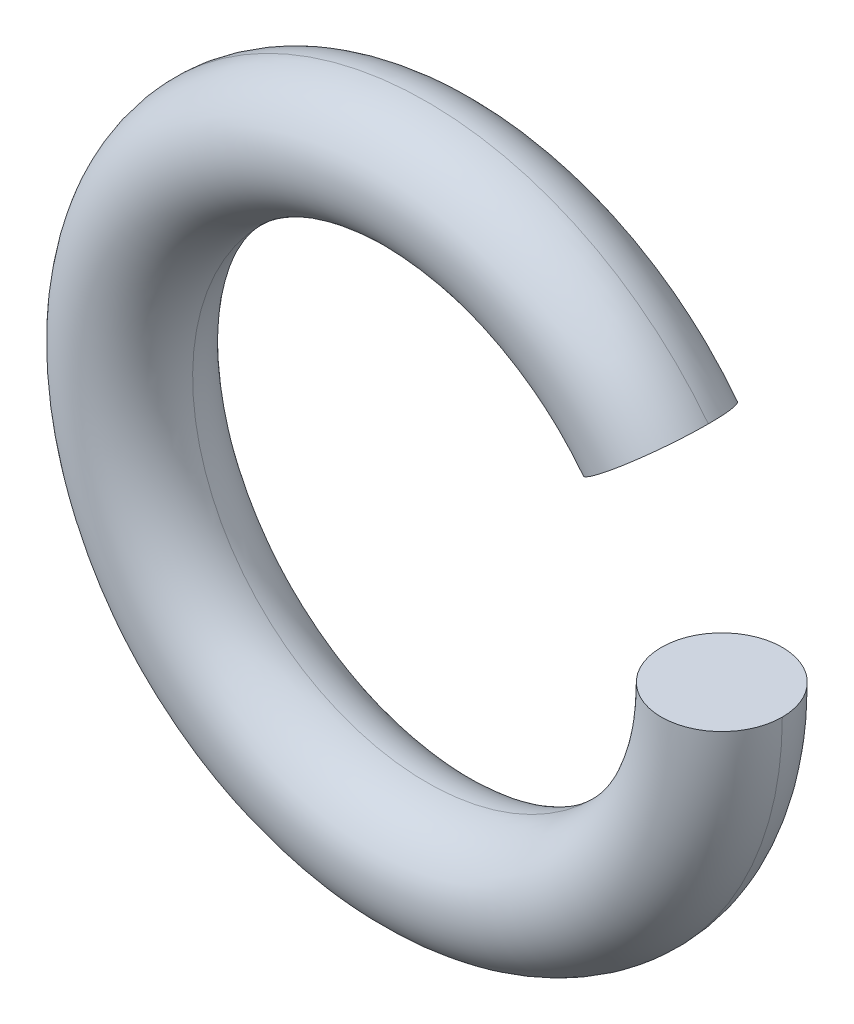
SolidWorks part; units mm, degrees
ref_plane "Front" through (0, 0, 0) normal (0, 0, 1) x (1, 0, 0)
ref_plane "Top" through (0, 0, 0) normal (0, 1, 0) x (1, 0, 0)
ref_plane "Right" through (0, 0, 0) normal (1, 0, 0) x (0, 0, -1)
sketch "Sketch1" plane through (0, 0, 0) normal (0, 0, 1) x (1, 0, 0)
  line L0 (-76.5339, 0) -> (24.9274, 0) construction
  line L1 (0, 65.6634) -> (0, -53.6178) construction
  line L2 (0, 0) -> (2.5652, 1.9782) construction
  arc A0 (1.2274, 0.9465) -> (1.55, 0) centre (0, 0) ccw
  dimension "d2" = 3.1
  dimension "e" = 1
sketch "Sketch2" plane through (0, 0, 0) normal (0, 1, 0) x (1, 0, 0)
  circle A0 centre (1.95, 0) radius 0.4
  point P2 (1.55, 0)
  dimension "d4" = 0.8
sweep "Sweep1" add profiles "Sketch2" path "Sketch1"
split line "Split Line3"
